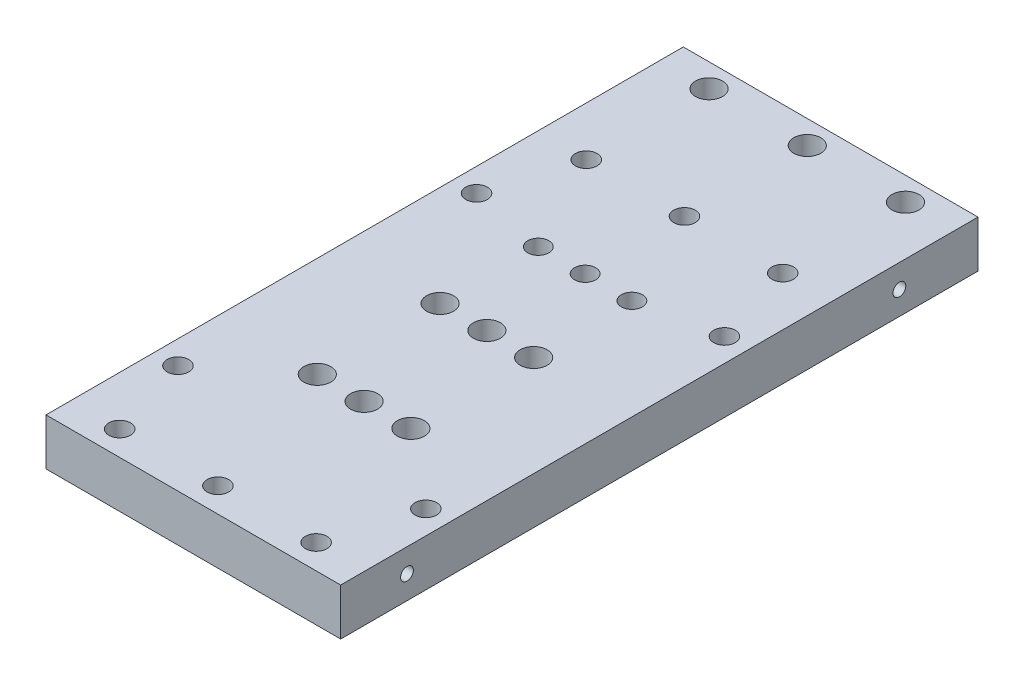
SolidWorks part; units mm, degrees
material "6061 Alloy"
ref_plane "Front Plane" through (0, 0, 0) normal (0, 0, 1) x (1, 0, 0)
ref_plane "Top Plane" through (0, 0, 0) normal (0, 1, 0) x (1, 0, 0)
ref_plane "Right Plane" through (0, 0, 0) normal (1, 0, 0) x (0, 0, -1)
sketch "Sketch1" plane through (0, 0, 0) normal (0, 1, 0) x (1, 0, 0)
  line L1 (-30, 80) -> (30, 80)
  line L2 (-30, 80) -> (-30, -80)
  line L3 (-30, -80) -> (30, -80)
  line L4 (30, 80) -> (30, -80)
  line L5 (0, -80) -> (0, 80) construction
  line L6 (-30, 0) -> (30, 0) construction
  point P0 (0, 0)
  dimension "D1" = 60
  dimension "D2" = 160
extrude "Boss-Extrude1" add sketch "Sketch1" along normal mid plane 9.53
sketch "Sketch3" plane through (0, 0, 0) normal (0, 1, 0) x (1, 0, 0)
  line L0 (0, 75.2375) -> (20, 75.2375) construction
  line L5 (0, -80) -> (0, 80) construction
  line L6 (-30, 0) -> (30, 0) construction
  line L7 (0, 50.2375) -> (20, 50.2375) construction
  line L8 (30, 80) -> (-30, 80) construction
  line L9 (-30, 80) -> (-30, -80) construction
  line L10 (-30, -80) -> (30, -80) construction
  line L11 (30, -80) -> (30, 80) construction
  line L12 (0, -44.7625) -> (20, -44.7625) construction
  circle A0 centre (20, 75.2375) radius 2.75
  circle A1 centre (20, 50.2375) radius 2.2
  circle A2 centre (-20, 50.2375) radius 2.2
  circle A3 centre (-20, 75.2375) radius 2.75
  circle A4 centre (0, 75.2375) radius 2.75
  circle A5 centre (0, 50.2375) radius 2.2
  circle A6 centre (20, -44.7625) radius 2.2
  circle A7 centre (-20, -44.7625) radius 2.2
  circle A8 centre (0, -44.7625) radius 2.2
  point P0 (0, 0)
  dimension "D4" = 5.5
  dimension "D5" = 4.4
  dimension "D1" = 4.7625
  dimension "D2" = 25
  dimension "D3" = 20
  dimension "D6" = 2
extrude "M4/5_through" cut sketch "Sketch3" against normal up to surface (4.765 mm away) and the other way blind 6.35 up to face at (0, -4.765, 0)
sketch "Sketch4" plane through (0, 0, -80) normal (0, 0, -1) x (-1, 0, 0)
  line L0 (0, 0) -> (-12, 0) construction
  line L1 (0, 0) -> (0, 4.765) construction
  line L2 (-30, 4.765) -> (30, 4.765) construction
  circle A0 centre (-12, 0) radius 1.3
  circle A1 centre (12, 0) radius 1.3
  dimension "D1" = 2.6
  dimension "D2" = 12
extrude "M3_DRILL" cut sketch "Sketch4" against normal blind 8
sketch "Sketch5" plane through (0, 4.765, 0) normal (0, 1, 0) x (1, 0, 0)
  line L0 (-20, -44.7625) -> (0, -44.7625) construction
  line L1 (-30, 80) -> (-30, -80) construction
  line L2 (0, 0) -> (0, -23.6676) construction
  line L3 (-20, 50.2375) -> (-20, -44.7625) construction
  line L4 (-20, 2.7375) -> (-9.1233, 2.7375) construction
  circle A0 centre (-25.2375, -27.6625) radius 2.2
  circle A1 centre (25.2375, -27.6625) radius 2.2
  circle A2 centre (25.2375, 33.1375) radius 2.2
  circle A3 centre (-25.2375, 33.1375) radius 2.2
  dimension "D2" = 4.4
  dimension "D1" = 17.1
  dimension "D3" = 4.7625
extrude "M4_through" cut sketch "Sketch5" against normal up to surface (9.53 mm away) up to face at (20, -4.765, -48.0375)
sketch "Sketch6" plane through (0, 4.765, 0) normal (0, 1, 0) x (1, 0, 0)
  line L0 (0, 0) -> (0, -64.4319) construction
  circle A0 centre (0, 30) radius 2.15
  circle A1 centre (9.53, 30) radius 2.15
  circle A2 centre (-9.53, 30) radius 2.15
  dimension "D1" = 4.3
  dimension "D4" = 30
  dimension "D2" = 2
  dimension "D3" = 2
extrude "M5_DRILL" cut sketch "Sketch6" against normal up to surface (9.53 mm away) up to face at (-25.2375, -4.765, -30.9375)
sketch "Sketch7" plane through (0, 4.765, 0) normal (0, 1, 0) x (1, 0, 0)
  line L0 (0, 30) -> (0, -15) construction
  circle A0 centre (0, 10) radius 2.75
  circle A1 centre (0, -15) radius 2.75
  circle A2 centre (9.53, 10) radius 2.75
  circle A3 centre (9.53, -15) radius 2.75
  circle A4 centre (-9.53, 10) radius 2.75
  circle A5 centre (-9.53, -15) radius 2.75
  dimension "D3" = 5.5
  dimension "D1" = 45
  dimension "D2" = 20
  dimension "D4" = 2
  dimension "D5" = 2
extrude "M5_through" cut sketch "Sketch7" against normal up to surface (9.53 mm away) up to face at (-9.53, -4.765, -27.85)
sketch "Sketch8" plane through (0, 4.765, 0) normal (0, 1, 0) x (1, 0, 0)
  line L0 (-20, -44.7625) -> (20, -44.7625) construction
  line L1 (30, -80) -> (30, 80) construction
  line L2 (-30, -80) -> (30, -80)
  line L3 (-30, -80) -> (-30, -49.7625)
  line L4 (-30, -49.7625) -> (30, -49.7625)
  line L5 (30, -80) -> (30, -49.7625)
  line L6 (0, -49.7625) -> (0, -80) construction
  line L7 (-30, -64.8812) -> (30, -64.8812) construction
  point P260 (0, -64.8812)
  dimension "D1" = 5
extrude "Cut-Extrude3" cut sketch "Sketch8" against normal up to surface (9.53 mm away) up to face at (-9.53, -4.765, -7.25)
sketch "Sketch9" plane through (-30, 0, 0) normal (-1, 0, 0) x (0, 0, 1)
  line L0 (-80, 0) -> (49.7625, 0) construction
  line L1 (-80, 4.765) -> (-80, -4.765) construction
  line L2 (49.7625, -4.765) -> (49.7625, 4.765) construction
  line L3 (36.2625, 0) -> (36.2625, 97.94) construction
  line L4 (-64, 0) -> (-64, 97.94) construction
  circle A0 centre (-64, 0) radius 1.3
  circle A1 centre (36.2625, 0) radius 1.3
  circle A2 centre (36.2625, 97.94) radius 1.3 construction
  dimension "D1" = 2.6
  dimension "D2" = 2.6
extrude "Cut-Extrude4" cut sketch "Sketch9" against normal blind 10
mirror "Mirror1" about plane through (0, 0, 0) normal (1, 0, 0) of "Cut-Extrude4"
